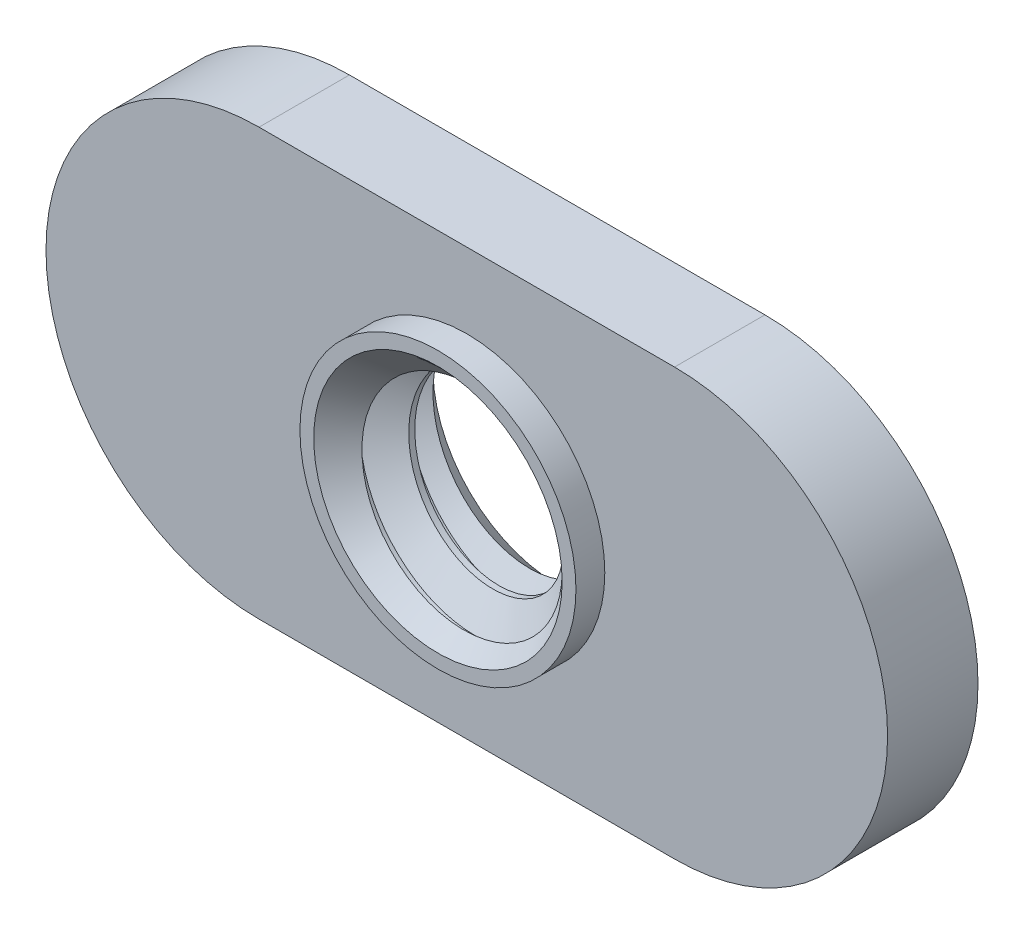
SolidWorks part; units mm, degrees
material "1.4310 (X10CrNi18-8)"
ref_plane "Front Plane" through (0, 0, 0) normal (0, 0, 1) x (1, 0, 0)
ref_plane "Top Plane" through (0, 0, 0) normal (0, 1, 0) x (1, 0, 0)
ref_plane "Right Plane" through (0, 0, 0) normal (1, 0, 0) x (0, 0, -1)
sketch "Sketch1" plane through (0, 0, 0) normal (0, 0, 1) x (1, 0, 0)
  line L0 (-11.1125, 0) -> (11.1125, 0) construction
  line L1 (0, -5.6261) -> (0, 5.6261) construction
  line L2 (0, 0) -> (0, -1.27) construction
  line L3 (0, 0) -> (-1.5875, -2.7496) construction
  circle A0 centre (0, 0) radius 3.175 construction
  circle A1 centre (0, 0) radius 3.6449 construction
  point P5 (0, 0)
  point P11 (-1.5875, -2.7496)
  dimension "Thread Size" = 6.35
  dimension "Boss Diameter" = 7.2898
  dimension "Length" = 22.225
  dimension "Width" = 11.2522
  dimension "Thread Pitch" = 1.27
  dimension "D1" = 30
sketch "Sketch2" plane through (0, 0, 0) normal (1, 0, 0) x (0, 0, -1)
  line L0 (1.5748, 0) -> (-1.5748, 0) construction
  point P0 (-0.8128, 0)
  point P3 (0, 0)
  dimension "Thickness" = 3.1496
  dimension "Boss Height" = 0.762
sketch "Sketch3" plane through (0, 0, 0) normal (0, 0, 1) x (1, 0, 0)
  line L0 (-5.4864, 0) -> (5.4864, 0) construction
  line L1 (-11.1125, 0) -> (11.1125, 0) construction
  line L2 (-5.4864, 5.6261) -> (5.4864, 5.6261)
  line L3 (-5.4864, -5.6261) -> (5.4864, -5.6261)
  arc A0 (-5.4864, 5.6261) -> (-5.4864, -5.6261) centre (-5.4864, 0) ccw
  arc A1 (5.4864, -5.6261) -> (5.4864, 5.6261) centre (5.4864, 0) ccw
  circle A2 centre (0, 0) radius 3.175 construction
  circle A3 centre (0, 0) radius 3.175
  point P4 (0, 0)
extrude "Boss-Extrude1" add sketch "Sketch3" along normal up to vertex (0.8128 mm away) from vertex up to point (0, 0, 0.8128) starting at point (0, 0, -1.5748)
sketch "Sketch4" plane through (0, 0, 0.8128) normal (0, 0, 1) x (1, 0, 0)
  circle A0 centre (0, 0) radius 3.6449
  circle A1 centre (0, 0) radius 3.175 construction
  circle A2 centre (0, 0) radius 3.175
  circle A3 centre (0, 0) radius 3.6449 construction
extrude "Boss-Extrude2" add sketch "Sketch4" along normal up to vertex (0.762 mm away) up to point (0, 0, 1.5748)
chamfer "Chamfer1" distance 0.1058 angle 45 2 edges at (3.175, 0, 1.5748) (3.175, 0, -1.5748)
sketch "Sketch5" plane through (0, 0, 1.5748) normal (0, 0, 1) x (1, 0, 0)
  circle A0 centre (0, 0) radius 3.175 construction
  circle A1 centre (0, 0) radius 3.175
curve "Helix/Spiral1" pitch 1.27 height 4.4196 radius 3.175 centre (0, 0, 1.5748) axis (0, 0, -1) start towards (0, 1, 0)
sketch "Sketch6" plane through (0, 0, 0) normal (1, 0, 0) x (0, 0, -1)
  line L0 (-2.7654, 3.3125) -> (-2.1304, 2.2126) construction
  line L1 (-2.1304, 2.2126) -> (-1.4954, 3.3125) construction
  line L2 (-1.4954, 3.3125) -> (-2.7654, 3.3125) construction
  line L3 (-2.6861, 3.175) -> (-1.5748, 3.175) construction
  line L4 (-2.1304, 3.3125) -> (-2.1304, 3.175) construction
  line L5 (-2.1304, 3.175) -> (-2.1304, 2.3501) construction
  line L6 (-2.1304, 2.3501) -> (-2.1304, 2.2126) construction
  line L7 (-2.2098, 2.3501) -> (-2.0511, 2.3501)
  line L8 (-2.7257, 3.2437) -> (-1.5351, 3.2437)
  line L9 (-2.0511, 2.3501) -> (-1.5351, 3.2437)
  line L10 (-2.2098, 2.3501) -> (-2.7257, 3.2437)
  line L11 (-1.5748, 3.175) -> (-1.5748, -3.175) construction
  line L12 (-1.5748, 3.175) -> (-1.5748, -3.175) construction
  point P12 (-2.1304, 3.2437)
  dimension "D1" = 1.27
  dimension "D2" = 0.1588
sweep "Sweep1" add profiles "Sketch6" path "Helix/Spiral1"
sketch "Sketch7" plane through (0, 0, 1.5748) normal (0, 0, 1) x (1, 0, 0)
  circle A0 centre (0, 0) radius 3.2808 construction
  circle A1 centre (0, 0) radius 3.2808
extrude "Cut-Extrude1" cut sketch "Sketch7" against normal through all draft 45 and the other way through all
sketch "Sketch8" plane through (0, 0, -1.5748) normal (0, 0, -1) x (-1, 0, 0)
  circle A0 centre (0, 0) radius 3.2808 construction
  circle A1 centre (0, 0) radius 3.2808
extrude "Cut-Extrude2" cut sketch "Sketch8" against normal through all draft 45 and the other way through all
equation "\"D1@Chamfer1\"=\"Thread Pitch@Sketch1\" / 12"
equation "\"D4@Helix/Spiral1\"=\"Thread Pitch@Sketch1\""
equation "\"D3@Helix/Spiral1\"=\"Thickness@Sketch2\" + \"Thread Pitch@Sketch1\""
equation "\"D2@Sketch6\"=\"D1@Sketch6\"/8"
equation "\"D1@Sketch6\"=\"Thread Pitch@Sketch1\""
